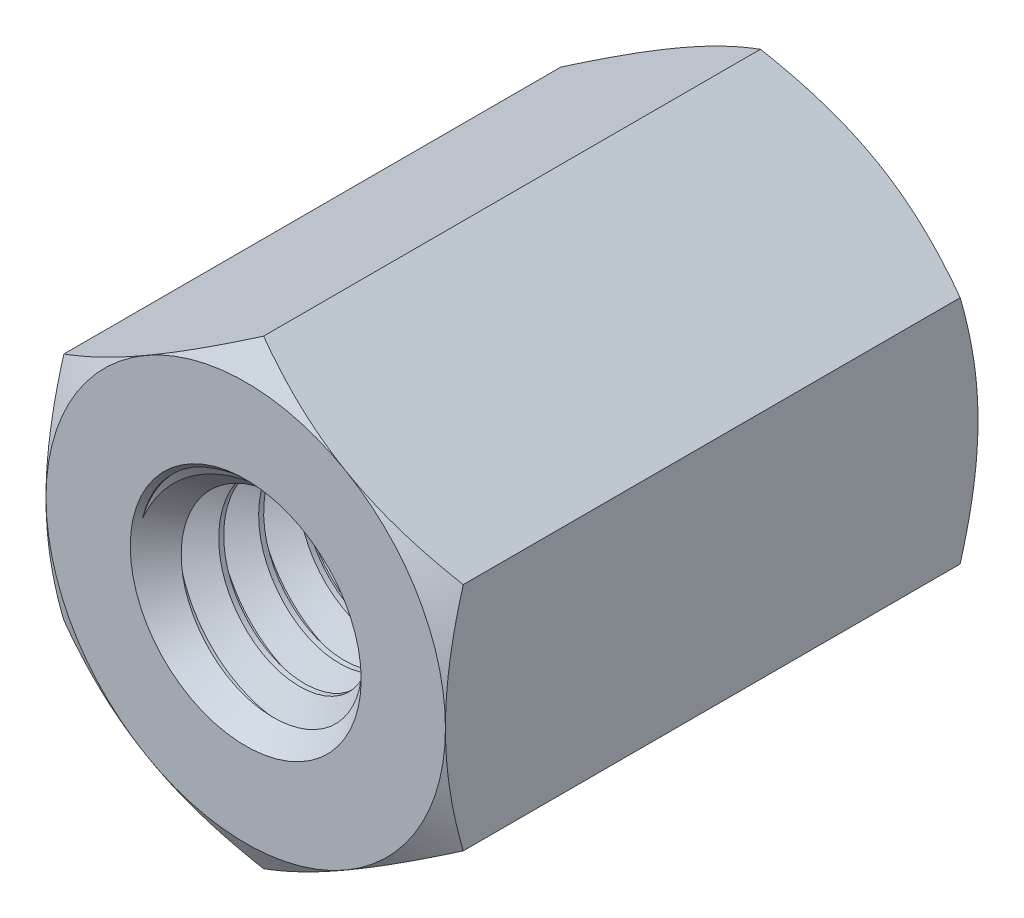
SolidWorks part; units mm, degrees
ref_plane "Front Plane" through (0, 0, 0) normal (0, 0, 1) x (1, 0, 0)
ref_plane "Top Plane" through (0, 0, 0) normal (0, 1, 0) x (1, 0, 0)
ref_plane "Right Plane" through (0, 0, 0) normal (1, 0, 0) x (0, 0, -1)
sketch "Sketch1" plane through (0, 0, 0) normal (1, 0, 0) x (0, 0, -1)
  line L0 (-3, 0) -> (3, 0) construction
  line L1 (0, 2.25) -> (0, -2.25) construction
  line L2 (-3, 1.25) -> (-3, -1.25) construction
  point P9 (3, 2.25)
  point P10 (-3, 2.25)
  dimension "Length" = 6
  dimension "Thread Dia" = 2.5
  dimension "Hex" = 4.5
sketch "Sketch19" plane through (0, 0, 0) normal (0, 0, 1) x (1, 0, 0)
  line L1 (0, 2.5981) -> (-2.25, 1.299)
  line L2 (-2.25, 1.299) -> (-2.25, -1.299)
  line L3 (-2.25, -1.299) -> (0, -2.5981)
  line L4 (0, -2.5981) -> (2.25, -1.299)
  line L5 (2.25, -1.299) -> (2.25, 1.299)
  line L6 (2.25, 1.299) -> (0, 2.5981)
  circle A0 centre (0, 0) radius 2.25 construction
  circle A1 centre (0, 0) radius 1.25
  point P10 (0, -1.25)
extrude "Extrude1" add sketch "Sketch19" along normal up to vertex (3 mm away) and the other way up to vertex (3 mm away) up to point (0, 0, 3) other way up to point (0, 0, -3)
sketch "Sketch8" plane through (0, 0, -3) normal (0, 0, -1) x (-1, 0, 0)
  circle A0 centre (0, 0) radius 2.25 construction
  circle A1 centre (0, 0) radius 2.25
extrude "Extrude4" cut sketch "Sketch8" against normal through all draft 60 flip side to cut
mirror "Mirror2" about plane through (0, 0, 0) normal (0, 0, 1) of "Extrude4"
sketch "Sketch11" plane through (0, 0, -3) normal (0, 0, -1) x (-1, 0, 0)
  circle A0 centre (0, 0) radius 1.25 construction
  circle A1 centre (0, 0) radius 1.25
curve "Helix/Spiral1" pitch 0.45 height 6.45 radius 1.25 centre (0, 0, -3) axis (0, 0, 1) start towards (0, 1, 0) parameters "Pitch"=0.45
sketch "Sketch12" plane through (0, 0, 0) normal (1, 0, 0) x (0, 0, -1)
  line L0 (3.3938, 1.25) -> (3, 1.25)
  line L1 (3.3938, 1.25) -> (3.225, 0.9577)
  line L2 (3.225, 0.9577) -> (3.1688, 0.9577)
  line L3 (3.1688, 0.9577) -> (3, 1.25)
  line L4 (3.1969, 0.9577) -> (3.1969, 1.25) construction
  line L5 (3.3094, 1.1039) -> (3.0844, 1.1039) construction
  dimension "D1" = 0.0563
  dimension "D2" = 0.225
  dimension "D3" = 60
sweep "Sweep1" add profiles "Sketch12" path "Helix/Spiral1"
sketch "Sketch6" plane through (0, 0, -3) normal (0, 0, -1) x (-1, 0, 0)
  arc A6 (-1.125, 1.9486) -> (-2.25, 0) centre (0, 0) ccw
  arc A7 (-1.125, 1.9486) -> (-2.25, 0) centre (0, 0) ccw
  arc A8 (-2.25, 0) -> (-1.125, -1.9486) centre (0, 0) ccw
  arc A9 (-2.25, 0) -> (-1.125, -1.9486) centre (0, 0) ccw
  arc A10 (-1.125, -1.9486) -> (1.125, -1.9486) centre (0, 0) ccw
  arc A11 (-1.125, -1.9486) -> (1.125, -1.9486) centre (0, 0) ccw
  arc A12 (1.125, -1.9486) -> (2.25, 0) centre (0, 0) ccw
  arc A13 (1.125, -1.9486) -> (2.25, 0) centre (0, 0) ccw
  arc A14 (2.25, 0) -> (1.125, 1.9486) centre (0, 0) ccw
  arc A15 (2.25, 0) -> (1.125, 1.9486) centre (0, 0) ccw
  arc A16 (1.125, 1.9486) -> (-1.125, 1.9486) centre (0, 0) ccw
  arc A17 (1.125, 1.9486) -> (-1.125, 1.9486) centre (0, 0) ccw
  dimension "D1" = 0
extrude "Extrude2" cut sketch "Sketch6" along normal through all
sketch "Sketch7" plane through (0, 0, -3) normal (0, 0, -1) x (-1, 0, 0)
  circle A2 centre (0, 0) radius 1.3008
  circle A3 centre (0, 0) radius 1.3008
  dimension "D1" = 0.0508
extrude "Extrude3" cut sketch "Sketch7" against normal through all draft 43
mirror "Mirror1" about plane through (0, 0, 0) normal (0, 0, 1) of "Extrude3", "Extrude2"
equation "\"D3@Helix/Spiral1\" = \"Length@Sketch1\" + \"Pitch@Helix/Spiral1\""
equation "\"D1@Sketch12\" = \"Pitch@Helix/Spiral1\"*.125"
equation "\"D2@Sketch12\" = \"Pitch@Helix/Spiral1\"*.5"
